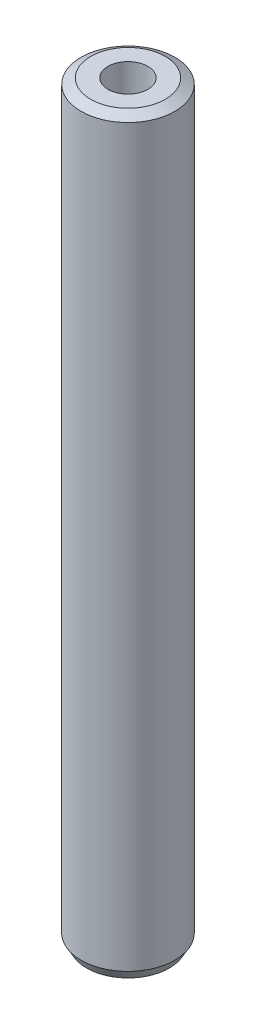
SolidWorks part; units mm, degrees
ref_plane "Front Plane" through (0, 0, 0) normal (0, 0, 1) x (1, 0, 0)
ref_plane "Top Plane" through (0, 0, 0) normal (0, 1, 0) x (1, 0, 0)
ref_plane "Right Plane" through (0, 0, 0) normal (1, 0, 0) x (0, 0, -1)
sketch "Sketch1" plane through (0, 0, 0) normal (0, 1, 0) x (1, 0, 0)
  circle A0 centre (0, 0) radius 37.5
  dimension "SHAFT_OD" = 75
extrude "Boss-Extrude1" add sketch "Sketch1" along normal blind 600
sketch "Sketch2" plane through (0, 0, 0) normal (0, 1, 0) x (1, 0, 0)
  circle A0 centre (0, 0) radius 15.9566
  dimension "BORE_D" = 31.9131
extrude "Cut-Extrude1" cut sketch "Sketch2" along normal through all
chamfer "Chamfer1" distance 4.4528 angle 60 2 edges at (0, 600, 37.5) (0, 0, 37.5) first distance on face at (0, 600, 37.5) first distance on face at (0, 0, 15.9566)
